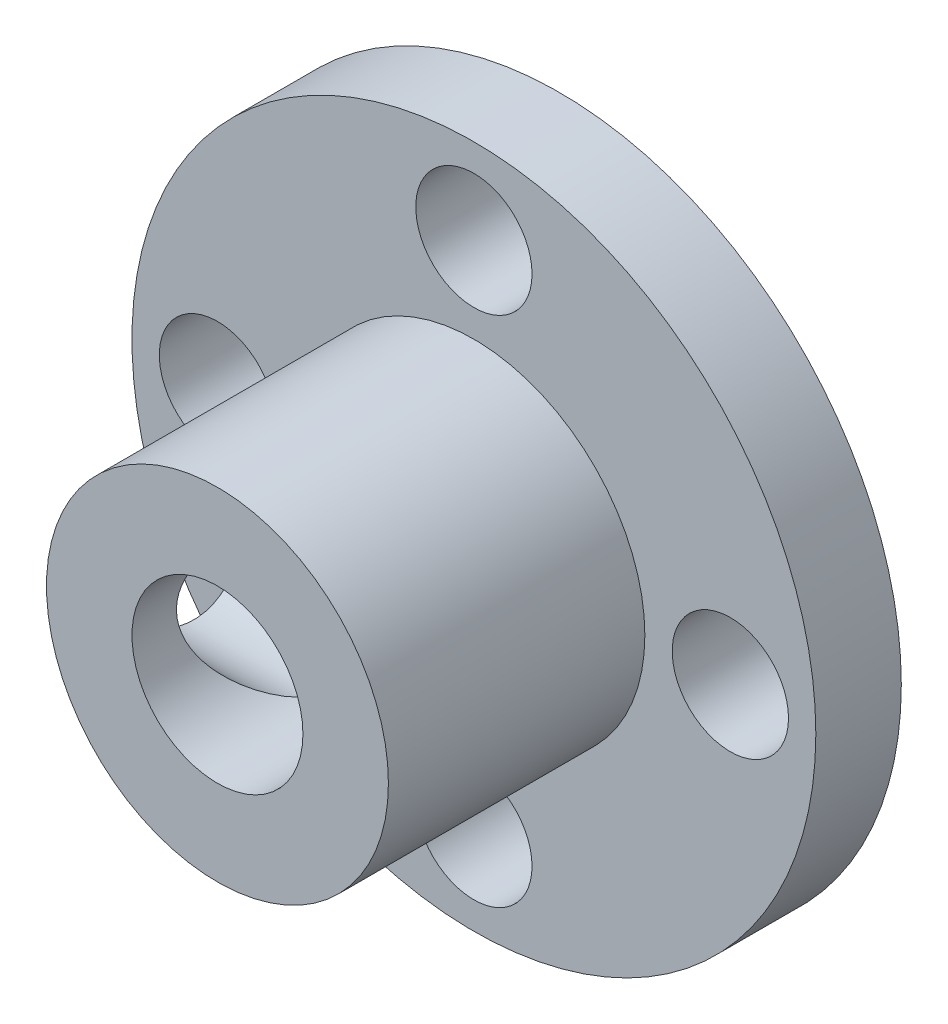
SolidWorks part; units mm, degrees
note: The reader was unsure of these and kept them because the rebuilt part matched: shared geometry of "Sketch2<3>".
ref_plane "Front Plane" through (0, 0, 0) normal (0, 0, 1) x (1, 0, 0)
ref_plane "Top Plane" through (0, 0, 0) normal (0, 1, 0) x (1, 0, 0)
ref_plane "Right Plane" through (0, 0, 0) normal (1, 0, 0) x (0, 0, -1)
sketch "Sketch2" plane through (0, 0, 0) normal (0, 0, 1) x (1, 0, 0)
  circle A0 centre (0, 0) radius 12.7
  circle A1 centre (0, 0) radius 3.175
  circle A2 centre (0, 0) radius 6.35
  circle A3 centre (0, 0) radius 9.525 construction
  circle A4 centre (0, 9.525) radius 2.159
  circle A5 centre (9.525, 0) radius 2.159
  circle A6 centre (0, -9.525) radius 2.159
  circle A7 centre (-9.525, 0) radius 2.159
  point P17 (0, 0)
  dimension "D1" = 6.35
  dimension "D2" = 25.4
  dimension "D3" = 12.7
  dimension "D4" = 19.05
  dimension "D5" = 4.318
  dimension "D6" = 4
extrude "Boss-Extrude1" add sketch "Sketch2" along normal blind 3.175 contours A2 A1 | A0 A7 A6 A5 A4 A2
extrude "Boss-Extrude2" add sketch "Sketch2<3>" along normal blind 12.7 contours A2 A1
sketch "Sketch2<3>" plane through (0, 0, 0) normal (0, 0, 1) x (1, 0, 0) same geometry as "Sketch2"
sketch "Sketch4" plane through (0, 0, 0) normal (1, 0, 0) x (0, 0, -1)
  line L0 (6.985, 0) -> (-6.985, 0) construction
  line L1 (-3.175, 12.7) -> (-3.175, -12.7) construction
  circle A0 centre (-8.001, 0) radius 3.048
  dimension "D1" = 6.096
  dimension "D2" = 4.826
extrude "Cut-Extrude1" cut sketch "Sketch4" against normal blind 12.7
